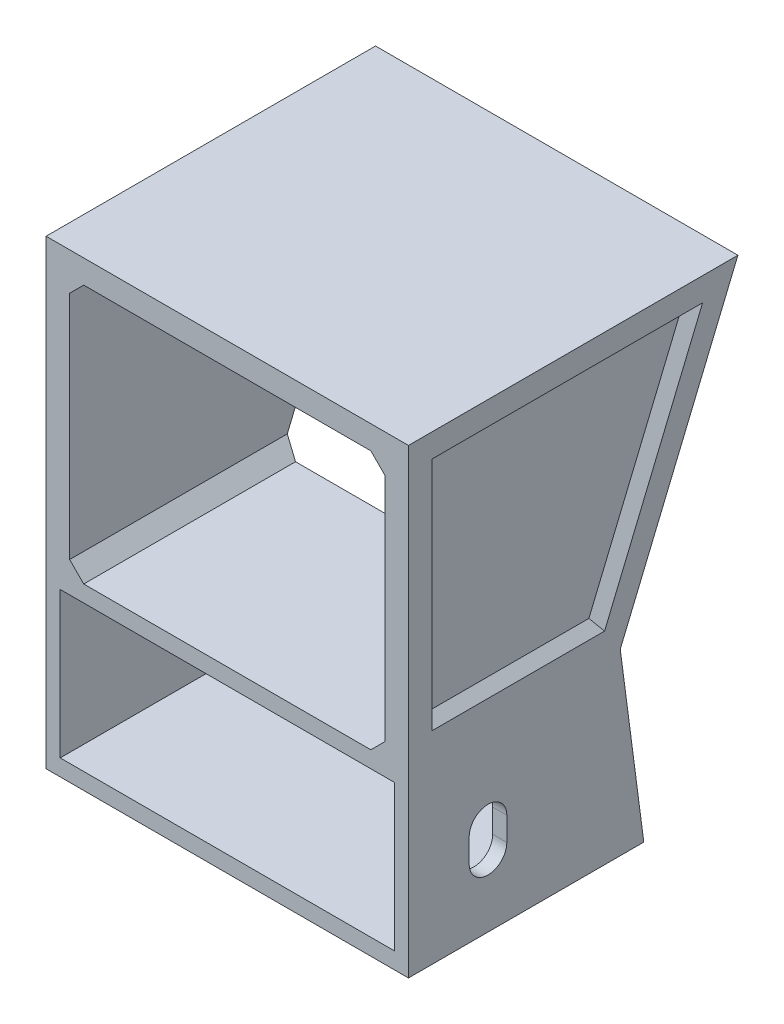
SolidWorks part; units mm, degrees
ref_plane "Ebene vorne" through (0, 0, 0) normal (0, 0, 1) x (1, 0, 0)
ref_plane "Ebene oben" through (0, 0, 0) normal (0, 1, 0) x (1, 0, 0)
ref_plane "Ebene rechts" through (0, 0, 0) normal (1, 0, 0) x (0, 0, -1)
sketch "Skizze1" plane through (0, 0, 0) normal (0, 0, 1) x (1, 0, 0)
  line L0 (0, 0) -> (0, 19) construction
  line L3 (-38.5, 19) -> (38.5, 19)
  line L5 (-38.5, -19) -> (38.5, -19)
  line L9 (38.5, 19) -> (38.5, -19)
  line L10 (-38.5, -19) -> (-38.5, 19)
  line L13 (0, 0) -> (-22.5, 0) construction
  line L14 (-22.5, -9) -> (22.5, -9) construction
  line L15 (-22.5, -9) -> (-22.5, 9) construction
  line L16 (-22.5, 9) -> (22.5, 9) construction
  line L17 (22.5, -9) -> (22.5, 9) construction
  line L18 (-22.5, -9) -> (22.5, 9) construction
  line L19 (-22.5, 9) -> (22.5, -9) construction
  point P27 (0, 0)
  dimension "D1" = 38
  dimension "D2" = 77
  dimension "D6" = 45
  dimension "D7" = 18
extrude "Aufsatz-Linear austragen1" add sketch "Skizze1" along normal mid plane 50
sketch "Skizze5" plane through (0, 0, -25) normal (0, 0, -1) x (-1, 0, 0)
  line L0 (-38.5, 0) -> (38.5, 0) construction
  line L3 (-38.5, 19) -> (38.5, 19) construction
  line L4 (38.5, -19) -> (-38.5, -19) construction
  line L5 (-20.32, 6.35) -> (-10.16, 6.35) construction
  line L6 (0, 19) -> (0, -19) construction
  line L7 (-38.5, -19) -> (-38.5, 19) construction
  line L8 (38.5, 19) -> (38.5, -19) construction
  circle A0 centre (-20.32, 6.35) radius 2.75
  circle A1 centre (-20.32, -6.35) radius 2.75
  circle A2 centre (-10.16, 6.35) radius 2.75
  circle A3 centre (-10.16, -6.35) radius 2.75
  circle A4 centre (0, 6.35) radius 2.75
  circle A5 centre (0, -6.35) radius 2.75
  circle A6 centre (10.16, 6.35) radius 2.75
  circle A7 centre (10.16, -6.35) radius 2.75
  circle A8 centre (20.32, 6.35) radius 2.75
  circle A9 centre (20.32, -6.35) radius 2.75
  dimension "D4" = 5.5
  dimension "D1" = 12.7
  dimension "D3" = 10.16
  dimension "D2" = 5
extrude "Schnitt-Linear austragen1" cut sketch "Skizze5" against normal through all
sketch "Skizze6" plane through (0, 0, 0) normal (1, 0, 0) x (0, 0, -1)
  line L4 (0, 19) -> (0, 0) construction
  line L6 (20, 19) -> (25, 19)
  line L7 (25, -19) -> (20, 19)
  line L8 (25, 19) -> (25, -19)
  line L9 (-25, -19) -> (25, -19) construction
  line L10 (-25, 19) -> (25, 19) construction
  line L11 (0, 0) -> (25, 0) construction
  dimension "D1" = 5
extrude "Schnitt-Linear austragen2" cut sketch "Skizze6" against normal through all both and the other way through all
sketch "Skizze8" plane through (0, 2.9101, -22.1171) normal (0, 0.1305, -0.9915) x (1, 0, 0)
  line L36 (23.07, -3.4695) -> (23.07, 9.34) construction
  line L38 (-33.5, 17.099) -> (33.5, 17.099)
  line L39 (-33.5, 17.099) -> (-33.5, -11.2285)
  line L40 (-33.5, -11.2285) -> (33.5, -11.2285)
  line L41 (33.5, 17.099) -> (33.5, -11.2285)
  line L42 (-33.5, 17.099) -> (33.5, -11.2285) construction
  line L43 (-33.5, -11.2285) -> (33.5, 17.099) construction
  line L47 (38.5, -16.2285) -> (38.5, 22.099) construction
  line L60 (-38.5, -16.2285) -> (38.5, -16.2285) construction
  line L61 (33.5, 2.9352) -> (0, 2.9352) construction
  line L62 (-38.5, 22.099) -> (38.5, 22.099) construction
  ellipse E0 centre (20.32, -3.4695) end of major axis (20.32, -6.2432) minor radius 2.75 construction
  ellipse E1 centre (20.32, 9.34) end of major axis (20.32, 12.1137) minor radius 2.75 construction
  point P8 (0, 2.9352)
  dimension "D1" = 5
  dimension "D2" = 5
extrude "Schnitt-Linear austragen8" cut sketch "Skizze8" against normal blind 3 draft 45
sketch "Skizze9" plane through (0, 0, 0) normal (0, 0, 1) x (1, 0, 0)
  line L0 (0, 0) -> (-35.5, 0) construction
  line L1 (-35.5, -15.5) -> (35.5, -15.5)
  line L2 (-35.5, -15.5) -> (-35.5, 15.5)
  line L3 (-35.5, 15.5) -> (35.5, 15.5)
  line L4 (35.5, -15.5) -> (35.5, 15.5)
  line L5 (-35.5, -15.5) -> (35.5, 15.5) construction
  line L6 (-35.5, 15.5) -> (35.5, -15.5) construction
  line L9 (-38.5, -19) -> (38.5, -19) construction
  line L10 (38.5, 19) -> (-38.5, 19) construction
  point P0 (0, 0)
  point P19 (23.07, 66.9034)
  dimension "D1" = 31
  dimension "D2" = 71
extrude "Schnitt-Linear austragen9" cut sketch "Skizze9" along normal through all and the other way offset from surface 4.5 other way up to face at (0, -0.3914, -19.5256)
sketch "Skizze10" plane through (0, 0, 0) normal (0, 0, 1) x (1, 0, 0)
  line L0 (-27.5, -15.5) -> (-27.5, 15.5)
  line L1 (-35.5, -15.5) -> (35.5, -15.5) construction
  line L3 (-27.5, 15.5) -> (-35.5, 15.5)
  line L4 (-35.5, 15.5) -> (-35.5, -15.5)
  line L5 (-35.5, 15.5) -> (-35.5, -15.5) construction
  line L7 (-35.5, -15.5) -> (-27.5, -15.5)
  line L8 (0, 88.7534) -> (0, 57.7534) construction
  line L10 (35.5, 15.5) -> (35.5, -15.5)
  line L11 (27.5, 15.5) -> (35.5, 15.5)
  line L12 (27.5, -15.5) -> (27.5, 15.5)
  line L13 (35.5, -15.5) -> (27.5, -15.5)
  line L14 (35.5, 15.5) -> (-35.5, 15.5) construction
  line L15 (35.5, 15.5) -> (-35.5, 15.5) construction
  dimension "D1" = 8
extrude "Aufsatz-Linear austragen2" add sketch "Skizze10" against normal up to surface from vertex up to face at (-20.32, -9.1, -16.1327) starting at point (-35.5, 15.5, -12.8959)
sketch "Skizze22" plane through (38.5, 0, 0) normal (1, 0, 0) x (0, 0, -1)
  line L0 (20, 19) -> (45, 79)
  line L1 (45, 79) -> (-25, 79)
  line L2 (-25, 79) -> (-25, 19)
  line L3 (20, 19) -> (-25, 19)
  dimension "D1" = 60
  dimension "D2" = 70
extrude "Aufsatz-Linear austragen4" add sketch "Skizze22" against normal up to surface (77 mm away) up to face at (-38.5, 0, 1.25)
sketch "Skizze23" plane through (0, 0, 25) normal (0, 0, 1) x (1, 0, 0)
  line L0 (-38.5, 19) -> (38.5, 19) construction
  line L1 (33.5, 19) -> (-33.5, 19)
  line L2 (33.5, 19) -> (33.5, 74)
  line L3 (33.5, 74) -> (-33.5, 74)
  line L4 (-33.5, 19) -> (-33.5, 74)
  line L5 (0, 79) -> (0, 19) construction
  line L7 (-38.5, 79) -> (38.5, 79) construction
  line L8 (38.5, -19) -> (38.5, 79) construction
  dimension "D1" = 5
  dimension "D2" = 5
extrude "Schnitt-Linear austragen19" cut sketch "Skizze23" against normal through all
sketch "Skizze24" plane through (38.5, 0, 0) normal (1, 0, 0) x (0, 0, -1)
  line L0 (16.6667, 24) -> (-20, 24)
  line L1 (-20, 24) -> (-20, 74)
  line L2 (-20, 74) -> (37.5, 74)
  line L3 (37.5, 74) -> (16.6667, 24)
  line L4 (20, 19) -> (45, 79) construction
  line L5 (45, 79) -> (-25, 79) construction
  line L6 (-25, -19) -> (-25, 79) construction
  dimension "D1" = 5
  dimension "D2" = 5
  dimension "D3" = 5
  dimension "D4" = 5
extrude "Schnitt-Linear austragen20" cut sketch "Skizze24" against normal blind 2 draft 45
mirror "Spiegeln9" about plane through (0, 0, 0) normal (1, 0, 0) of "Schnitt-Linear austragen20"
chamfer "Fase2" distance 3 angle 45 4 edges at (33.5, 19, 2.5) (-33.5, 19, 2.5) (33.5, 74, -8.9583) (-33.5, 74, -8.9583)
sketch "Skizze25" plane through (35.5, 0, 0) normal (-1, 0, 0) x (0, 0, 1)
  line L0 (8.1041, -4.5) -> (8.1041, 0.5) construction
  line L5 (4.1041, -4.5) -> (4.1041, 0.5)
  line L6 (12.1041, -4.5) -> (12.1041, 0.5)
  line L7 (8.1041, -8.5) -> (18.1782, -8.5) construction
  line L8 (8.1041, 4.5) -> (18.1782, 4.5) construction
  line L9 (-12.8959, -15.5) -> (-12.8959, 15.5) construction
  line L10 (25, -15.5) -> (-12.8959, -15.5) construction
  arc A0 (4.1041, -4.5) -> (12.1041, -4.5) centre (8.1041, -4.5) ccw
  arc A1 (12.1041, 0.5) -> (4.1041, 0.5) centre (8.1041, 0.5) ccw
  point P2 (8.1041, -2)
  dimension "D1" = 8
  dimension "D2" = 13
  dimension "D3" = 17
  dimension "D4" = 7
extrude "Schnitt-Linear austragen21" cut sketch "Skizze25" against normal up to surface (3 mm away) up to face at (38.5, 49, -3.5417)
